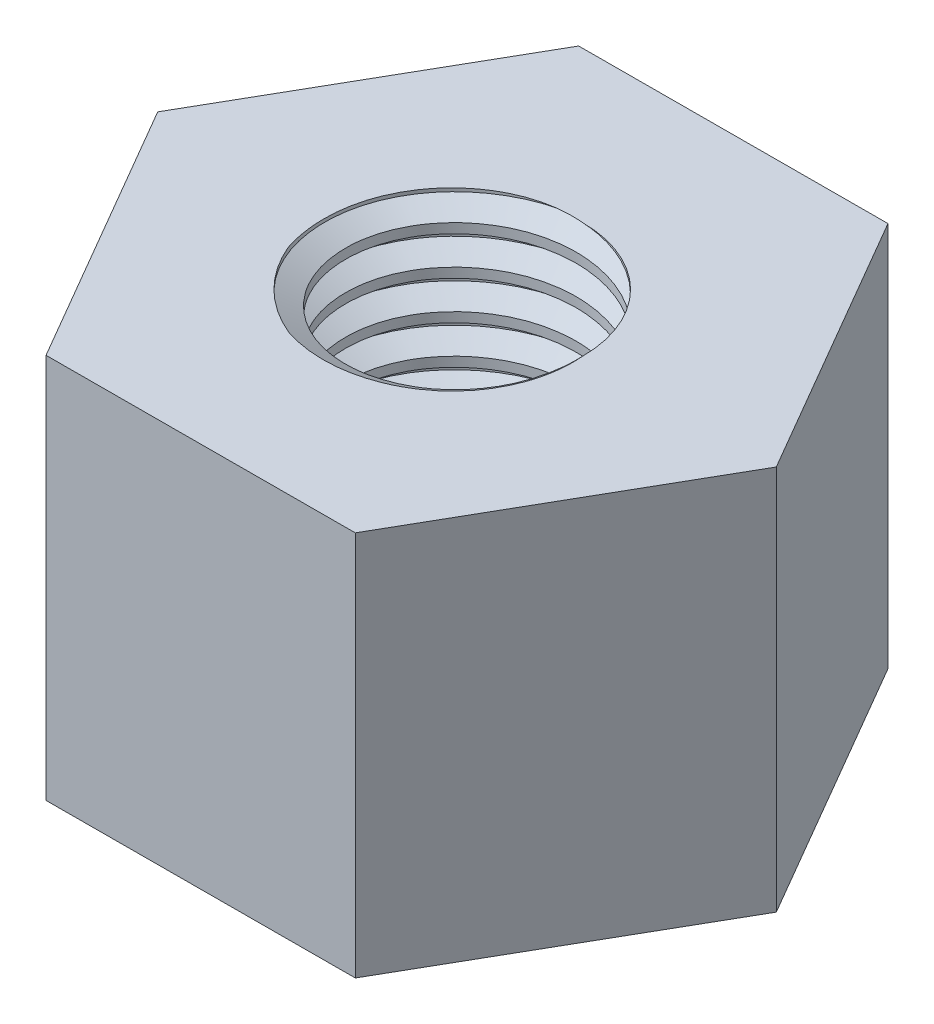
SolidWorks part; units mm, degrees
ref_plane "前视基准面" through (0, 0, 0) normal (0, 0, 1) x (1, 0, 0)
ref_plane "上视基准面" through (0, 0, 0) normal (0, 1, 0) x (1, 0, 0)
ref_plane "右视基准面" through (0, 0, 0) normal (1, 0, 0) x (0, 0, -1)
sketch "草图1" plane through (0, 0, 0) normal (0, 1, 0) x (1, 0, 0)
  line L1 (2.0098, -3.4584) -> (4, 0.0114)
  line L2 (4, 0.0114) -> (1.9902, 3.4698)
  line L3 (1.9902, 3.4698) -> (-2.0098, 3.4584)
  line L4 (-2.0098, 3.4584) -> (-4, -0.0114)
  line L5 (-4, -0.0114) -> (-1.9902, -3.4698)
  line L6 (-1.9902, -3.4698) -> (2.0098, -3.4584)
  circle A0 centre (0, 0) radius 3.4641 construction
  dimension "D1" = 4
extrude "凸台-拉伸1" add sketch "草图1" along normal blind 5
sketch "草图2" plane through (0, 0, 0) normal (0, -1, 0) x (1, 0, 0)
  circle A0 centre (0, 0) radius 1.5
  dimension "D1" = 3
extrude "切除-拉伸1" cut sketch "草图2" against normal blind 10
sketch "草图3" plane through (0, 5, 0) normal (0, 1, 0) x (1, 0, 0)
  circle A0 centre (0, 0) radius 1.5
  dimension "D1" = 3
thread "螺纹线1" pitch 0.5 method cut profile "螺纹线轮廓1" start angle 0, offset 0, length 8, pitch 0.5, diameter 3
ref_plane "基准面1" through (1.5, 0, 0) normal (0, 0, 1) x (1, 0, 0)
sketch "螺纹线轮廓1" plane through (1.5, 0, 0) normal (0, 0, 1) x (1, 0, 0)
  line L0 (0, 0) -> (0, 0.5) construction
  line L1 (0, 0) -> (0.2706, 0.1562)
  line L2 (0.2706, 0.1562) -> (0.2706, 0.2187)
  line L3 (0.2706, 0.2187) -> (0, 0.375)
  line L4 (0.2706, 0.1875) -> (0, 0.1875) construction
  line L11 (0, 0) -> (0, 0.375)
  point P2 (0, 0)
  dimension "Pitch" = 0.5
  dimension "Profile_Angle" = 60
  dimension "Profile_Land" = 0.0625
  dimension "Profile_Height" = 0.2706
